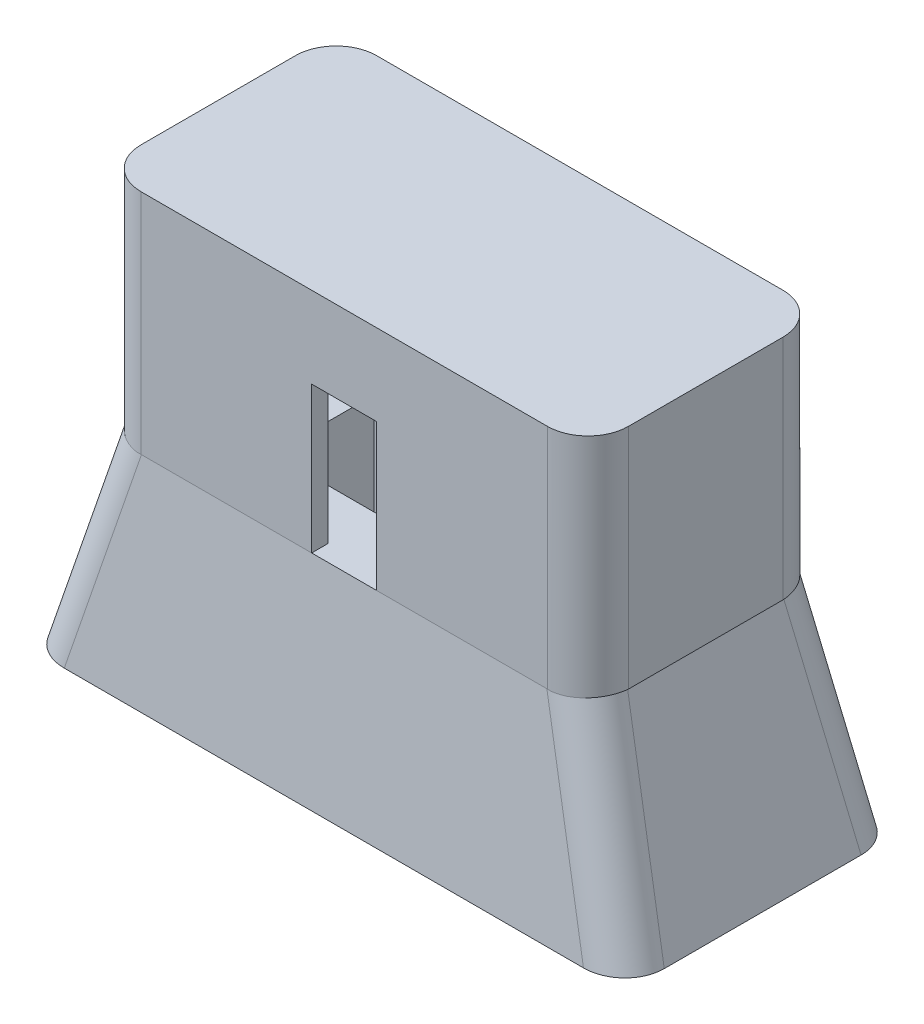
SolidWorks part; units mm, degrees
ref_plane "Front Plane" through (0, 0, 0) normal (0, 0, 1) x (1, 0, 0)
ref_plane "Top Plane" through (0, 0, 0) normal (0, 1, 0) x (1, 0, 0)
ref_plane "Right Plane" through (0, 0, 0) normal (1, 0, 0) x (0, 0, -1)
sketch "Sketch1" plane through (0, 0, 0) normal (0, 1, 0) x (1, 0, 0)
  line L1 (37, 17) -> (-37, 17)
  line L2 (37, 17) -> (37, -17)
  line L3 (37, -17) -> (-37, -17)
  line L4 (-37, 17) -> (-37, -17)
  line L5 (37, 17) -> (-37, -17) construction
  line L6 (37, -17) -> (-37, 17) construction
  point P0 (0, 0)
  dimension "D1" = 34
  dimension "D2" = 74
ref_plane "Plane1" through (0, 25, 0) normal (0, 1, 0) x (1, 0, 0)
sketch "Sketch5" plane through (0, 25, 0) normal (0, 1, 0) x (1, 0, 0)
  line L1 (30, 14.5) -> (-30, 14.5)
  line L2 (30, 14.5) -> (30, -14.5)
  line L3 (30, -14.5) -> (-30, -14.5)
  line L4 (-30, 14.5) -> (-30, -14.5)
  line L5 (30, 14.5) -> (-30, -14.5) construction
  line L6 (30, -14.5) -> (-30, 14.5) construction
  point P0 (0, 0)
  dimension "D1" = 29
  dimension "D2" = 60
loft "Loft2" add profiles "Sketch5", "Sketch1" connector at (-30, 25, -14.5) connector at (-37, 0, -17)
sketch "Sketch6" plane through (0, 0, 0) normal (0, 1, 0) x (1, 0, 0)
  line L0 (-30, -14.5) -> (30, -14.5) construction
  line L1 (30, 14.5) -> (-30, 14.5)
  line L2 (30, 14.5) -> (30, -14.5)
  line L3 (30, -14.5) -> (4, -14.5)
  line L4 (-30, 14.5) -> (-30, -14.5)
  line L5 (-4, -12.5) -> (-4, -14.5)
  line L6 (4, -12.5) -> (4, -14.5)
  line L7 (-30, 14.5) -> (-30, -14.5) construction
  line L8 (-4, -12.5) -> (-28, -12.5)
  line L9 (28, 12.5) -> (-28, 12.5)
  line L10 (28, 12.5) -> (28, -12.5)
  line L11 (28, -12.5) -> (4, -12.5)
  line L12 (-28, 12.5) -> (-28, -12.5)
  line L13 (-4, -14.5) -> (-30, -14.5)
  point P0 (0, 0)
  point P10 (0, 0)
  dimension "D1" = 2
  dimension "D2" = 2
  dimension "D3" = 8
  dimension "D4" = 26
  dimension "D5" = 29
extrude "Boss-Extrude1" add sketch "Sketch6" along normal blind 28 from surface starting at face at (0, 25, 0)
sketch "Sketch7" plane through (0, 0, 0) normal (0, -1, 0) x (1, 0, 0)
  line L0 (0, 0) -> (37, 0) construction
  line L1 (37, 17) -> (37, -17) construction
  line L2 (0, 0) -> (0, 17.0572) construction
  circle A0 centre (15.5, 8) radius 1.75
  circle A1 centre (15.5, -8) radius 1.75
  circle A2 centre (-15.5, -8) radius 1.75
  circle A3 centre (-15.5, 8) radius 1.75
  dimension "D1" = 8
  dimension "D2" = 15.5
extrude "Cut-Extrude1" cut sketch "Sketch7" against normal blind 25
sketch "Sketch8" plane through (0, 0, 0) normal (0, -1, 0) x (1, 0, 0)
  line L5 (-37, -17) -> (-37, 17) construction
  line L6 (-22, 6.2) -> (12, 6.2)
  line L7 (-22, 6.2) -> (-22, -6.2)
  line L8 (-22, -6.2) -> (12, -6.2)
  line L9 (12, 6.2) -> (12, -6.2)
  line L10 (-22, 6.2) -> (12, -6.2) construction
  line L11 (-22, -6.2) -> (12, 6.2) construction
  line L12 (37, -17) -> (-37, -17) construction
  point P0 (-5, 0)
  dimension "D1" = 12.4
  dimension "D2" = 34
  dimension "D3" = 15
  dimension "D4" = 10.8
extrude "Cut-Extrude5" cut sketch "Sketch8" against normal blind 10.2
sketch "Sketch9" plane through (0, 0, 0) normal (0, -1, 0) x (1, 0, 0)
  line L0 (-22, 6.2) -> (-22, -6.2) construction
  line L1 (-17, 6.3) -> (7, 6.3)
  line L2 (-17, 6.3) -> (-17, -6.2)
  line L3 (-17, -6.2) -> (7, -6.2)
  line L4 (7, 6.3) -> (7, -6.2)
  line L5 (12, -6.2) -> (12, 6.2) construction
  line L6 (-22, -6.2) -> (12, -6.2) construction
  dimension "D1" = 5
  dimension "D2" = 5
  dimension "D3" = 12.5
  dimension "D4" = 0
extrude "Cut-Extrude6" cut sketch "Sketch9" against normal blind 16 from surface starting at face at (-5, 10.2, 0)
fillet "Fillet3" radius 5 8 edges
sketch "Sketch12" plane through (0, 25, 0) normal (0, 1, 0) x (1, 0, 0)
  line L1 (7, 6.2) -> (12, 6.2)
  line L2 (7, 6.2) -> (7, -6.3)
  line L3 (7, -6.3) -> (12, -6.3)
  line L4 (12, 6.2) -> (12, -6.3)
  dimension "D1" = 12.5
  dimension "D2" = 5
extrude "Cut-Extrude9" cut sketch "Sketch12" against normal blind 7
sketch "Sketch13" plane through (0, 0, -14.5) normal (0, 0, -1) x (-1, 0, 0)
  line L0 (18.7001, 25) -> (-18.7001, 25) construction
  line L1 (-7.75, 30.1) -> (7.75, 30.1)
  line L2 (-7.75, 30.1) -> (-7.75, 27.5)
  line L3 (-7.75, 27.5) -> (7.75, 27.5)
  line L4 (7.75, 30.1) -> (7.75, 27.5)
  line L5 (-25, 53) -> (-25, 24.9975) construction
  dimension "D1" = 15.5
  dimension "D2" = 2.6
  dimension "D3" = 2.5
  dimension "D4" = 17.25
extrude "Cut-Extrude10" cut sketch "Sketch13" against normal blind 3
sketch "Sketch14" plane through (0, 53, 0) normal (0, 1, 0) x (1, 0, 0)
  line L0 (-4, -12.5) -> (-4, -14.5)
  line L1 (-28, 12.5) -> (28, 12.5)
  line L2 (-28, 12.5) -> (-28, -12.5)
  line L3 (-28, -12.5) -> (-4, -12.5)
  line L4 (28, 12.5) -> (28, -12.5)
  line L5 (-4, -14.5) -> (-4, -12.5) construction
  line L6 (-4, -14.5) -> (4, -14.5)
  line L7 (4, -14.5) -> (4, -12.5)
  line L8 (4, -12.5) -> (28, -12.5)
extrude "Boss-Extrude2" add sketch "Sketch14" against normal blind 10
